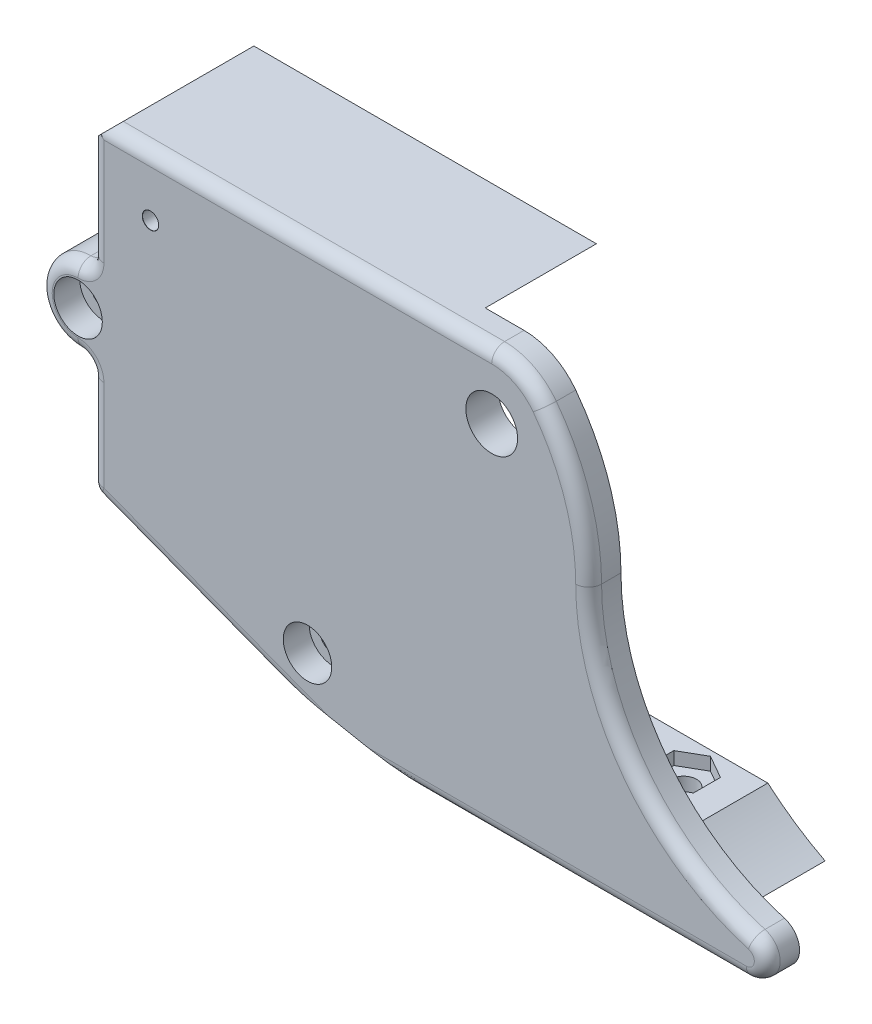
SolidWorks part; units mm, degrees
ref_plane "Front Plane" through (0, 0, 0) normal (0, 0, 1) x (1, 0, 0)
ref_plane "Top Plane" through (0, 0, 0) normal (0, 1, 0) x (1, 0, 0)
ref_plane "Right Plane" through (0, 0, 0) normal (1, 0, 0) x (0, 0, -1)
sketch "Sketch1" plane through (0, 0, 0) normal (0, 0, 1) x (1, 0, 0)
  line L0 (0, -40) -> (-72.5, -40) construction
  line L2 (-112, 25) -> (-112, -25)
  line L3 (-72.5, -40) -> (-20.6155, -40)
  line L4 (-102, 21) -> (-60, 21) construction
  line L5 (-102, 21) -> (-102, -21) construction
  line L6 (-102, -21) -> (-60, -21) construction
  line L7 (-60, 21) -> (-60, -21) construction
  line L8 (-102, 21) -> (-60, -21) construction
  line L9 (-102, -21) -> (-60, 21) construction
  line L10 (-29.4788, -34) -> (-77.0327, -34)
  line L11 (-108, -22.2403) -> (-108, 21)
  line L12 (-108, 21) -> (-60, 21)
  line L13 (-72.5, -40) -> (-112, -25)
  line L14 (-77.0327, -34) -> (-108, -22.2403)
  line L15 (-112, 25) -> (-56, 25)
  arc A0 (-22.016, 33.3961) -> (0, -40) centre (0, 0) cw construction
  arc A1 (-22.016, 33.3961) -> (-60, 21) centre (-63.6326, 96.5245) cw construction
  circle A4 centre (0, 0) radius 40 construction
  arc A6 (-20.6155, -40) -> (-29.4788, -34) centre (0, 0) cw
  circle A10 centre (-50, 15) radius 11 construction
  arc A11 (-60, 21) -> (-56, 25) centre (-50, 15) cw
  point P10 (-81, 0)
  point P25 (-112, 0)
  dimension "D1" = 40
  dimension "D3" = 52
  dimension "D8" = 45
  dimension "D12" = 4
  dimension "D13" = 22
  dimension "D2" = 72.5
  dimension "D4" = 50
  dimension "D5" = 42
  dimension "D6" = 42
  dimension "D7" = 81
  dimension "D9" = 6
  dimension "D10" = 4
  dimension "D11" = 4
  dimension "D14" = 50
  dimension "D15" = 15
extrude "Boss-Extrude1" add sketch "Sketch1" along normal blind 17.2
chamfer "Chamfer3" distance 3 angle 45 1 edges at (-112, 25, 8.6)
chamfer "Chamfer2" distance 2 angle 45 1 edges at (-108, 21, 8.6)
sketch "Sketch2" plane through (0, 0, 17.2) normal (0, 0, 1) x (1, 0, 0)
  line L1 (-72.5, -40) -> (-20.6155, -40)
  line L4 (-20.6155, -40) -> (-10.6155, -40)
  line L10 (-56, 25) -> (-109, 25)
  line L11 (-50, 25) -> (-109, 25)
  line L12 (-112, 22) -> (-112, -25)
  line L14 (-72.5, -40) -> (-20.6155, -40)
  line L15 (-29.4788, -34) -> (-77.0327, -34)
  line L16 (-112, -25) -> (-72.5, -40)
  line L17 (-108, -22.2403) -> (-108, 19)
  line L18 (-108, 19) -> (-106, 21)
  line L19 (-106, 21) -> (-60, 21)
  line L22 (-112, 22) -> (-112, -25)
  line L24 (-72.5, -40) -> (0, -40) construction
  line L33 (-112, -25) -> (-72.5, -40)
  line L34 (-77.0327, -34) -> (-108, -22.2403)
  line L35 (-109, 25) -> (-112, 22)
  line L36 (-109, 25) -> (-112, 22)
  circle A0 centre (-50, 15) radius 4
  arc A1 (-56, 25) -> (-60, 21) centre (-50, 15) ccw construction
  arc A2 (0, -40) -> (-23.5728, 32.316) centre (0, 0) ccw construction
  arc A6 (-29.4788, -34) -> (-20.6155, -40) centre (0, 0) ccw
  arc A8 (-56, 25) -> (-60, 21) centre (-50, 15) ccw
  circle A16 centre (-78.5, -30) radius 2.1
  arc A23 (-35, 0) -> (-9.7132, -33.6252) centre (0, 0) ccw
  arc A25 (-35, 0) -> (-42, 21) centre (-70, 0) ccw
  arc A26 (-42, 21) -> (-50, 25) centre (-50, 15) ccw
  arc A28 (-10.6155, -40) -> (-9.7132, -33.6252) centre (-10.6155, -36.7487) ccw
  dimension "D2" = 8
  dimension "D3" = 40
  dimension "D4" = 35
  dimension "D7" = 4.2
  dimension "D6" = 10
  dimension "D9" = 30
  dimension "D10" = 78.5
  dimension "D1" = 0
extrude "Boss-Extrude2" add sketch "Sketch2" along normal blind 5
ref_axis "Axis1" through (0, 0, 40.7637) along (0, 0, -1)
sketch "Sketch10" plane through (0, 0, 17.2) normal (0, 0, -1) x (-1, 0, 0)
  line L0 (83.5, -30) -> (83.5, -34)
  line L1 (73.5, -30) -> (73.5, -34)
  line L2 (29.4788, -34) -> (77.0327, -34) construction
  line L4 (73.5, -34) -> (83.5, -34)
  arc A0 (73.5, -30) -> (83.5, -30) centre (78.5, -30) cw
  circle A3 centre (78.5, -30) radius 2.1
  circle A4 centre (78.5, -30) radius 2.1 construction
  dimension "D1" = 10
extrude "Boss-Extrude8" add sketch "Sketch10" along normal up to surface (17.2 mm away) up to face at (-80.921, -5.1882, 0)
sketch "Sketch11" plane through (0, 0, 22.2) normal (0, 0, 1) x (1, 0, 0)
  circle A0 centre (-78.5, -30) radius 3.75
  dimension "D1" = 7.5
extrude "Cut-Extrude2" cut sketch "Sketch11" against normal blind 4
sketch "Sketch12" plane through (0, 0, 22.2) normal (0, 0, 1) x (1, 0, 0)
  line L0 (-114, 4.5) -> (-112, 4.5)
  line L2 (-112, 4.5) -> (-112, -7.5)
  line L3 (-112, -7.5) -> (-114, -7.5)
  line L6 (-112, 22) -> (-112, -25) construction
  arc A0 (-114, 4.5) -> (-114, -7.5) centre (-114, -1.5) ccw
  point P9 (-112, -1.5)
  point P15 (-112, -1.5)
  dimension "D1" = 6
  dimension "D2" = 2
extrude "Boss-Extrude9" add sketch "Sketch12" against normal up to surface (22.2 mm away) up to face at (-80.5346, -9.9202, 0)
fillet "Fillet3" radius 2 2 edges at (-112, -7.5, 11.1) (-112, 4.5, 11.1)
sketch "Sketch13" plane through (0, 0, 22.2) normal (0, 0, 1) x (1, 0, 0)
  circle A0 centre (-114, -1.5) radius 2
  dimension "D1" = 4
extrude "Cut-Extrude3" cut sketch "Sketch13" against normal up to surface (22.2 mm away) up to face at (-87.6416, -8.1475, 0)
sketch "Sketch14" plane through (0, 0, 22.2) normal (0, 0, 1) x (1, 0, 0)
  circle A0 centre (-114, -1.5) radius 3.75
  dimension "D1" = 7.5
extrude "Cut-Extrude4" cut sketch "Sketch14" against normal blind 4
sketch "Sketch15" plane through (0, -40, 0) normal (0, -1, 0) x (1, 0, 0)
  line L0 (-72.5, 0) -> (-20.6155, 0) construction
  circle A0 centre (-37.5, 5) radius 2
  dimension "D1" = 4
  dimension "D2" = 5
  dimension "D3" = 37.5
extrude "Cut-Extrude5" cut sketch "Sketch15" against normal up to surface (6 mm away) up to face at (-51.4894, -34, 8.6)
fillet "Fillet4" radius 2 2 edges at (-73.5, -34, 8.6) (-83.5, -31.5441, 8.6)
sketch "草图1" plane through (0, -34, 0) normal (0, 1, 0) x (1, 0, 0)
  line L0 (-37.5, -9.1569) -> (-33.9, -7.0785)
  line L1 (-33.9, -7.0785) -> (-33.9, -2.9071)
  line L2 (-33.9, -2.9071) -> (-37.5125, -0.8503)
  line L3 (-37.5125, -0.8503) -> (-41.1, -2.9215)
  line L4 (-41.1, -2.9215) -> (-41.1, -7.0785)
  line L5 (-41.1, -7.0785) -> (-37.5, -9.1569)
  circle A2 centre (-37.5, -5) radius 3.6 construction
  circle A3 centre (-37.5, -5) radius 2 construction
  dimension "D2" = 7.2
extrude "切除-拉伸1" cut sketch "草图1" against normal blind 2
ref_plane "基准面1" through (0, 0, 22.2) normal (0, 0, 1) x (1, 0, 0)
sketch "草图3" plane through (0, 0, 22.2) normal (0, 0, 1) x (1, 0, 0)
  line L0 (-54.849, 150.305) -> (0, 0) construction
  arc A0 (-74.5352, 146.7758) -> (-27.654, -11.63) centre (663.6959, 279.1196) ccw construction
  arc A2 (-27.654, -11.63) -> (28.6449, 8.9145) centre (0, 0) ccw construction
  arc A3 (-29.9652, -1.4453) -> (29.9652, -1.4453) centre (0, 0) ccw construction
  arc A4 (28.6449, 8.9145) -> (-37.5167, 160.2845) centre (-687.4781, -213.9483) ccw construction
  arc A6 (-74.5352, 146.7758) -> (-37.5167, 160.2845) centre (-54.849, 150.305) cw construction
  circle A7 centre (-50, 15) radius 11 construction
  dimension "D1" = 750
  dimension "D2" = 750
  dimension "D4" = 20
  dimension "D3" = 160
chamfer "倒角1" distance 15 angle 10 1 edges at (-72.5, -40, 11.1) first distance on face at (-92.25, -32.5, 11.1)
chamfer "倒角2" distance 5 angle 5 1 edges at (-86.5229, -34.6748, 11.1) first distance on face at (-72.5574, -37.3374, 11.1)
fillet "圆角2" radius 2 6 edges at (-34.6037, -40, 22.2) (-7.3964, -37.2044, 22.2) (-27.9729, -21.0361, 22.2) (-36.7961, 11.068, 22.2) (-45.5279, 23.9443, 22.2) (-79.5, 25, 22.2)
fillet "圆角3" radius 2 5 edges at (-112, -17.25, 22.2) (-112.5858, -8.0858, 22.2) (-120, -1.5, 22.2) (-112.5858, 5.0858, 22.2) (-112, 14.25, 22.2)
fillet "圆角4" radius 2 3 edges at (-112, -25, 10.1) (-111.4142, -25.2225, 21.6142) (-100.5986, -29.3296, 22.2)
hole_wizard "M3 螺纹孔的螺纹孔钻头1" positions "草图4" profile "草图5" hole size "M3" standard "ISO" end condition through all
sketch "草图4" plane through (0, 0, 22.2) normal (0, 0, 1) x (1, 0, 0)
  point P0 (-102.7947, 15.8169)
sketch "草图5" plane through (-102.7947, 15.8169, 22.2) normal (1, 0, 0) x (0, -1, 0)
  line L0 (0, 0) -> (0, 22.2)
  line L1 (0, 22.2) -> (1.25, 22.2)
  line L2 (1.25, 22.2) -> (1.25, 0.025)
  line L3 (1.25, 0.025) -> (1.275, 0)
  line L5 (1.275, 0) -> (0, 0)
  line L6 (-1.25, 0.025) -> (-1.275, 0) construction
  line L11 (0, -6.35) -> (0, 107.95) construction
  dimension "通孔孔直径" = 2.5
  dimension "通孔孔深度" = 22.2
  dimension "近端锥形沉头孔直径" = 2.55
  dimension "近端锥形沉头孔角度" = 90
